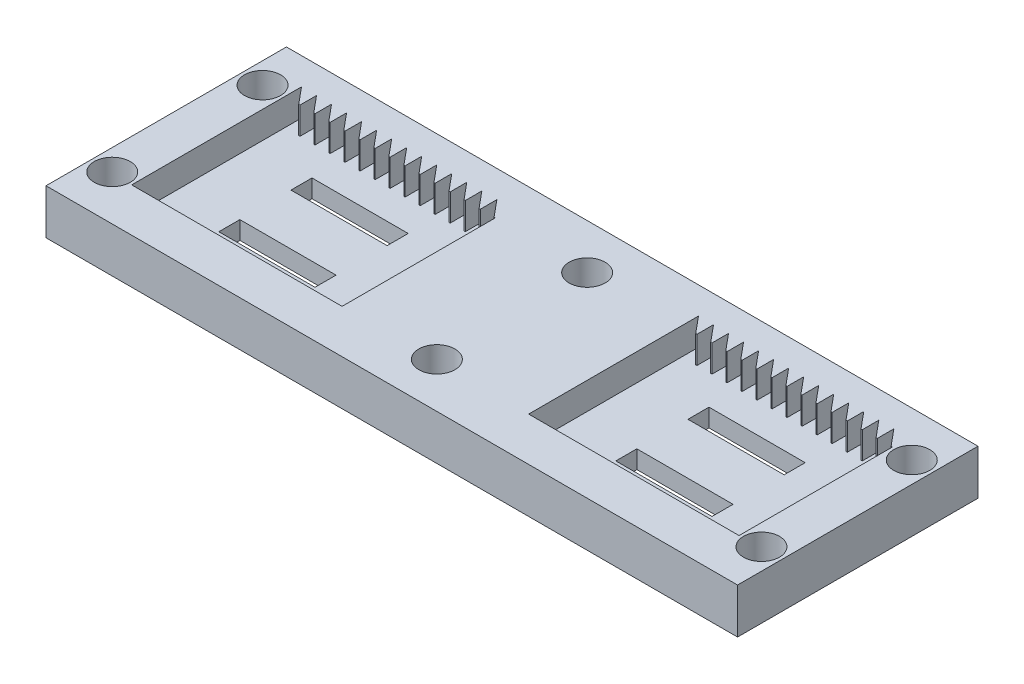
SolidWorks part; units mm, degrees
ref_plane "Front Plane" through (0, 0, 0) normal (0, 0, 1) x (1, 0, 0)
ref_plane "Top Plane" through (0, 0, 0) normal (0, 1, 0) x (1, 0, 0)
ref_plane "Right Plane" through (0, 0, 0) normal (1, 0, 0) x (0, 0, -1)
sketch "Sketch2" plane through (0, 0, 0) normal (0, 1, 0) x (1, 0, 0)
  line L0 (-15.52, 12.5) -> (-18.02, 15.5)
  line L1 (-57.52, 20) -> (57.52, 20)
  line L2 (-57.52, 20) -> (-57.52, -20)
  line L3 (-57.52, -20) -> (57.52, -20)
  line L4 (57.52, 20) -> (57.52, -20)
  line L5 (-50.52, 12.75) -> (-15.52, 12.75)
  line L6 (-50.52, 12.75) -> (-50.52, -12.75)
  line L7 (-50.52, -12.75) -> (-15.52, -12.75)
  line L8 (-15.52, 12.75) -> (-15.52, -12.75)
  line L9 (-57.52, 0) -> (-50.52, 0) construction
  line L10 (-18.02, 15.5) -> (-18.02, 12.5)
  line L11 (-18.02, 12.5) -> (-20.52, 15.5)
  line L12 (-20.52, 15.5) -> (-20.52, 12.5)
  line L13 (-20.52, 12.5) -> (-23.02, 15.5)
  line L14 (-23.02, 15.5) -> (-23.02, 12.5)
  line L15 (-23.02, 12.5) -> (-25.52, 15.5)
  line L16 (-25.52, 15.5) -> (-25.52, 12.5)
  line L17 (-25.52, 12.5) -> (-28.02, 15.5)
  line L18 (-28.02, 15.5) -> (-28.02, 12.5)
  line L19 (-28.02, 12.5) -> (-30.52, 15.5)
  line L20 (-30.52, 15.5) -> (-30.52, 12.5)
  line L21 (-30.52, 12.5) -> (-33.02, 15.5)
  line L22 (-33.02, 15.5) -> (-33.02, 12.5)
  line L23 (-33.02, 12.5) -> (-35.52, 15.5)
  line L24 (-35.52, 15.5) -> (-35.52, 12.5)
  line L25 (-35.52, 12.5) -> (-38.02, 15.5)
  line L26 (-38.02, 15.5) -> (-38.02, 12.5)
  line L27 (-38.02, 12.5) -> (-40.52, 15.5)
  line L28 (-40.52, 15.5) -> (-40.52, 12.5)
  line L29 (-40.52, 12.5) -> (-43.02, 15.5)
  line L30 (-43.02, 15.5) -> (-43.02, 12.5)
  line L31 (-43.02, 12.5) -> (-45.52, 15.5)
  line L32 (-45.52, 15.5) -> (-45.52, 12.5)
  line L33 (-45.52, 12.5) -> (-48.02, 15.5)
  line L34 (-48.02, 15.5) -> (-48.02, 12.5)
  line L35 (-48.02, 12.5) -> (-50.52, 15.5)
  line L36 (-50.52, 15.5) -> (-50.52, 12.5)
  line L37 (0, 0) -> (0, 9.3891) construction
  line L38 (50.52, 12.5) -> (48.02, 15.5)
  line L39 (57.52, 0) -> (50.52, 0) construction
  line L40 (15.52, 12.75) -> (50.52, 12.75)
  line L41 (-33.02, 12.75) -> (-33.02, -12.75) construction
  line L42 (15.52, 12.75) -> (15.52, -12.75)
  line L43 (15.52, -12.75) -> (50.52, -12.75)
  line L44 (50.52, 12.75) -> (50.52, -12.75)
  line L45 (3.0979, 0) -> (15.52, 0) construction
  line L46 (48.02, 15.5) -> (48.02, 12.5)
  line L47 (45.52, 15.5) -> (45.52, 12.5)
  line L48 (48.02, 12.5) -> (45.52, 15.5)
  line L49 (43.02, 15.5) -> (43.02, 12.5)
  line L50 (45.52, 12.5) -> (43.02, 15.5)
  line L51 (40.52, 15.5) -> (40.52, 12.5)
  line L52 (43.02, 12.5) -> (40.52, 15.5)
  line L53 (38.02, 15.5) -> (38.02, 12.5)
  line L54 (40.52, 12.5) -> (38.02, 15.5)
  line L55 (35.52, 15.5) -> (35.52, 12.5)
  line L56 (38.02, 12.5) -> (35.52, 15.5)
  line L57 (33.02, 15.5) -> (33.02, 12.5)
  line L58 (35.52, 12.5) -> (33.02, 15.5)
  line L59 (30.52, 15.5) -> (30.52, 12.5)
  line L60 (33.02, 12.5) -> (30.52, 15.5)
  line L61 (28.02, 15.5) -> (28.02, 12.5)
  line L62 (30.52, 12.5) -> (28.02, 15.5)
  line L63 (25.52, 15.5) -> (25.52, 12.5)
  line L64 (28.02, 12.5) -> (25.52, 15.5)
  line L65 (23.02, 15.5) -> (23.02, 12.5)
  line L66 (25.52, 12.5) -> (23.02, 15.5)
  line L67 (20.52, 15.5) -> (20.52, 12.5)
  line L68 (23.02, 12.5) -> (20.52, 15.5)
  line L69 (18.02, 15.5) -> (18.02, 12.5)
  line L70 (20.52, 12.5) -> (18.02, 15.5)
  line L71 (15.52, 15.5) -> (15.52, 12.5)
  line L72 (18.02, 12.5) -> (15.52, 15.5)
  line L73 (33.02, 12.75) -> (33.02, -12.75) construction
  line L74 (0, 20) -> (0, -20) construction
  line L75 (-15.52, 0) -> (0, 0) construction
  line L76 (0, 0) -> (15.52, 0) construction
  point P4 (0, 20)
  point P5 (-57.52, 0)
  point P46 (0, 0)
  dimension "D1" = 7
  dimension "D2" = 40
  dimension "D3" = 17.5
  dimension "D4" = 33.02
  dimension "D5" = 17.5
  dimension "D6" = 2.5
  dimension "D7" = 3
  dimension "D8" = 25.5
  dimension "D9" = 12.5
  dimension "D10" = 17.5
  dimension "D11" = 17.5
  dimension "D12" = 12.5
  dimension "D13" = 2.5
  dimension "D14" = 3
  dimension "D15" = 14
extrude "Boss-Extrude1" add sketch "Sketch2" against normal blind 3 contours L1 L4 L3 L2
ref_plane "Plane1" through (-57.52, 0, -20) normal (1, 0, 0) x (0, 0, -1)
extrude "Boss-Extrude2" add sketch "Sketch2<3>" along normal blind 4.5 contours L4 L1 L2 L3 L8 L7 L6 L5 region at (0.0157, 0, 0.4419)
sketch "Sketch2<3>" plane through (0, 0, 0) normal (0, 1, 0) x (1, 0, 0) same geometry as "Sketch2"
sketch "Sketch3" plane through (0, 0, 0) normal (0, 1, 0) x (1, 0, 0)
  line L0 (-50.52, 15.5) -> (-50.52, -12.75) construction
  line L1 (-50.52, 7.75) -> (50.52, 7.75)
  line L2 (-50.52, 7.75) -> (-50.52, 4.25)
  line L3 (-50.52, 4.25) -> (50.52, 4.25)
  line L4 (50.52, 7.75) -> (50.52, 4.25)
  line L5 (50.52, 12.75) -> (50.52, -12.75) construction
  line L6 (-50.52, 0) -> (-44.0832, 0) construction
  line L7 (-41.02, 4.25) -> (-41.02, 7.75)
  line L8 (-25.02, 4.25) -> (-25.02, 7.75)
  line L9 (-15.52, 12.75) -> (-15.52, -12.75) construction
  line L10 (0, 4.25) -> (0, -3.7317) construction
  line L11 (-25.02, -4.25) -> (-25.02, -7.75)
  line L12 (-41.02, -4.25) -> (-41.02, -7.75)
  line L13 (-50.52, -4.25) -> (50.52, -4.25)
  line L14 (50.52, -7.75) -> (50.52, -4.25)
  line L15 (-50.52, -7.75) -> (50.52, -7.75)
  line L16 (-50.52, -7.75) -> (-50.52, -4.25)
  line L17 (25.02, -4.25) -> (25.02, -7.75)
  line L18 (41.02, -4.25) -> (41.02, -7.75)
  line L19 (41.02, 4.25) -> (41.02, 7.75)
  line L20 (25.02, 4.25) -> (25.02, 7.75)
  line L21 (-50.52, 15.5) -> (-50.52, -12.75) construction
  line L22 (-50.52, 15.5) -> (-50.52, -12.75)
  point P10 (-50.52, 6)
  dimension "D1" = 3.5
  dimension "D2" = 6
  dimension "D3" = 9.5
  dimension "D4" = 9.5
extrude "Cut-Extrude1" cut sketch "Sketch3" against normal through all contours L3 L8 L1 L7 | L12 L15 L11 L13 | L20 L3 L19 L1 | L18 L13 L17 L15 region at (-33.02, 0, -6) region at (33.02, 0, -6) region at (-33.02, 0, 6) region at (33.02, 0, 6)
sketch "Sketch4" plane through (0, 4.5, 0) normal (0, 1, 0) x (1, 0, 0)
  line L0 (-57.52, 20) -> (57.52, -20) construction
  line L1 (57.52, 20) -> (-57.52, -20) construction
  line L2 (0, 12.5) -> (0, 0) construction
  circle A0 centre (0, 12.5) radius 1.75
  circle A2 centre (54, 12.5) radius 1.75
  circle A3 centre (54, -12.5) radius 1.75
  circle A4 centre (0, -12.5) radius 1.75
  circle A5 centre (-54, 12.5) radius 1.75
  circle A6 centre (-54, -12.5) radius 1.75
  dimension "D1" = 3.5
  dimension "D2" = 2
  dimension "D3" = 12.5
  dimension "D4" = 2
  dimension "D5" = 2
extrude "Cut-Extrude3" cut sketch "Sketch4" against normal through all contours A5 | A6 | A0 | A4 | A3 | A2 region at (0, 4.5, -12.5) region at (54, 4.5, -12.5) region at (54, 4.5, 12.5) region at (0, 4.5, 12.5) region at (-54, 4.5, -12.5) region at (-54, 4.5, 12.5)
sketch "Sketch5" plane through (0, 4.5, 0) normal (0, 1, 0) x (1, 0, 0)
  circle A0 centre (-54, 12.5) radius 3
  circle A1 centre (0, 12.5) radius 3
  circle A2 centre (54, 12.5) radius 3
  circle A3 centre (54, -12.5) radius 3
  circle A4 centre (0, -12.5) radius 3
  circle A5 centre (-54, -12.5) radius 3
  dimension "D1" = 6
extrude "Cut-Extrude4" cut sketch "Sketch5" against normal offset from surface (4.5 mm away) 3 up to face at (54, -3, 14.25)
